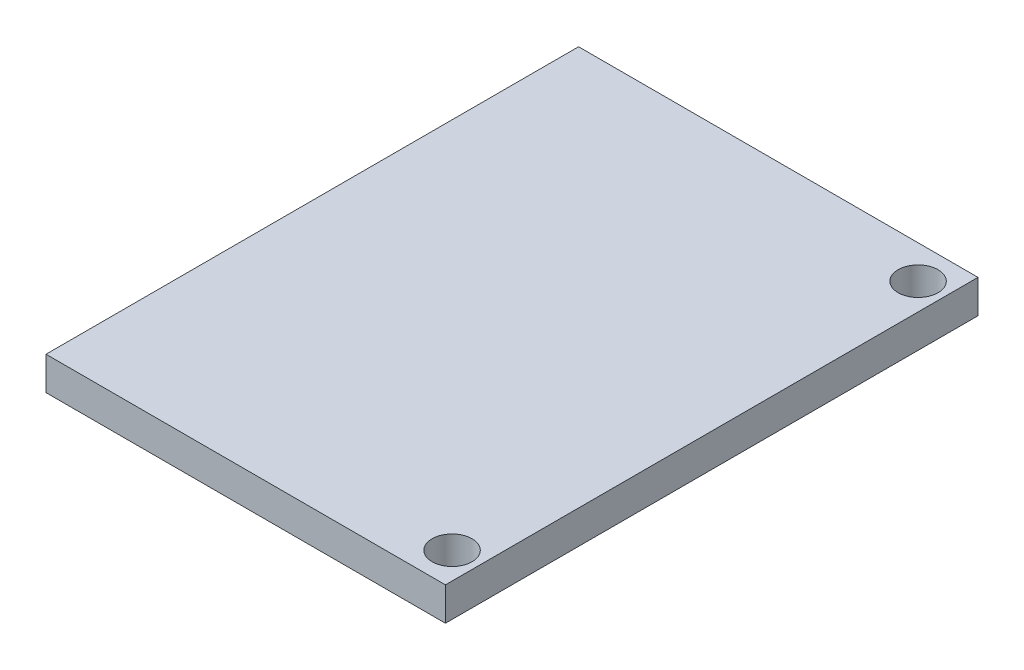
SolidWorks part; units mm, degrees
ref_plane "Front Plane" through (0, 0, 0) normal (0, 0, 1) x (1, 0, 0)
ref_plane "Top Plane" through (0, 0, 0) normal (0, 1, 0) x (1, 0, 0)
ref_plane "Right Plane" through (0, 0, 0) normal (1, 0, 0) x (0, 0, -1)
sketch "Sketch1" plane through (0, 0, 0) normal (0, 1, 0) x (1, 0, 0)
  line L1 (0, 0) -> (76.2, 0)
  line L2 (0, 0) -> (0, 101.6)
  line L3 (0, 101.6) -> (76.2, 101.6)
  line L4 (76.2, 0) -> (76.2, 101.6)
  dimension "D1" = 76.2
  dimension "D2" = 101.6
extrude "Boss-Extrude1" add sketch "Sketch1" along normal blind 6.35
sketch "Sketch2" plane through (0, 6.35, 0) normal (0, 1, 0) x (1, 0, 0)
  line L0 (71.12, 0) -> (71.12, 101.6) construction
  line L1 (0, 0) -> (76.2, 0) construction
  line L2 (76.2, 101.6) -> (0, 101.6) construction
  line L3 (0, 6.35) -> (76.2, 6.35) construction
  line L4 (0, 101.6) -> (0, 0) construction
  line L5 (76.2, 0) -> (76.2, 101.6) construction
  line L6 (0, 95.25) -> (76.2, 95.25) construction
  circle A0 centre (71.12, 95.25) radius 3.81
  circle A1 centre (71.12, 6.35) radius 3.81
  point P18 (0, 0)
  dimension "D4" = 7.62
  dimension "D1" = 6.35
  dimension "D2" = 6.35
  dimension "D3" = 5.08
extrude "Cut-Extrude1" cut sketch "Sketch2" against normal through all
